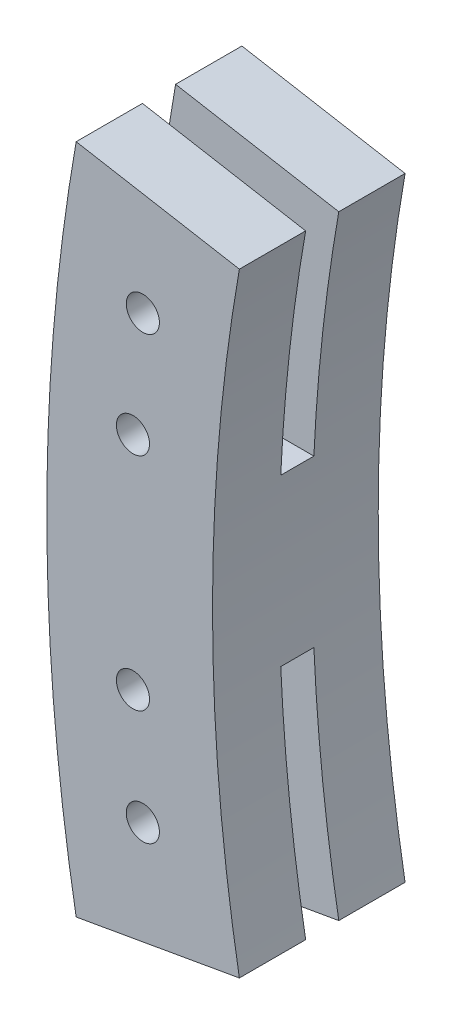
SolidWorks part; units mm, degrees
ref_plane "Front Plane" through (0, 0, 0) normal (0, 0, 1) x (1, 0, 0)
ref_plane "Top Plane" through (0, 0, 0) normal (0, 1, 0) x (1, 0, 0)
ref_plane "Right Plane" through (0, 0, 0) normal (1, 0, 0) x (0, 0, -1)
sketch "Sketch1" plane through (0, 0, 0) normal (0, 0, 1) x (1, 0, 0)
  line L0 (160, 0) -> (-167.5, 0) construction
  line L1 (0, 160) -> (0, -160) construction
  line L2 (0, 0) -> (-157.5692, 27.7837) construction
  line L3 (0, 0) -> (-157.5692, -27.7837) construction
  line L4 (-157.5692, 27.7837) -> (-172.3414, 30.3884)
  line L5 (-157.5692, -27.7837) -> (-172.3414, -30.3884)
  arc A0 (-157.5692, 27.7837) -> (-157.5692, -27.7837) centre (0, 0) ccw
  arc A1 (-172.3414, 30.3884) -> (-172.3414, -30.3884) centre (0, 0) ccw
  circle A2 centre (0, 0) radius 167.5 construction
  dimension "D1" = 320
  dimension "D2" = 350
  dimension "D4" = 7.5
  dimension "D3" = 20
extrude "Boss-Extrude3" add sketch "Sketch1" along normal mid plane 15 contours L4 A1 A0 | A1 L5 A0 | A1 A0 region at (-166.7623, 0, 0)
extrude "Cut-Extrude4" cut sketch "Sketch1<6>" against normal mid plane 3
sketch "Sketch1<6>" plane through (0, 0, 0) normal (0, 0, 1) x (1, 0, 0) same geometry as "Sketch1"
sketch "Sketch6" plane through (0, 0, 0) normal (0, 0, 1) x (1, 0, 0)
  line L1 (-184.1488, 7.5) -> (-150.8512, 7.5)
  line L2 (-184.1488, 7.5) -> (-184.1488, -7.5)
  line L3 (-184.1488, -7.5) -> (-150.8512, -7.5)
  line L4 (-150.8512, 7.5) -> (-150.8512, -7.5)
  line L5 (-184.1488, 7.5) -> (-150.8512, -7.5) construction
  line L6 (-184.1488, -7.5) -> (-150.8512, 7.5) construction
  arc A0 (-172.3414, 30.3884) -> (-172.3414, -30.3884) centre (0, 0) ccw construction
  arc A1 (-157.5692, 27.7837) -> (-157.5692, -27.7837) centre (0, 0) ccw construction
  arc A2 (-172.3414, 30.3884) -> (-172.3414, -30.3884) centre (0, 0) ccw
  arc A3 (-157.5692, 27.7837) -> (-157.5692, -27.7837) centre (0, 0) ccw
  point P0 (-167.5, 0)
  dimension "D1" = 15
extrude "Boss-Extrude5" add sketch "Sketch6" along normal mid plane 3 contours A3 L1 A2 L3 region at (-167.4439, 0, 0)
ref_plane "Plane1" through (-167.5, 0, 0) normal (1, 0, 0) x (0, 0, -1)
sketch "Sketch4" plane through (-167.5, 0, 0) normal (1, 0, 0) x (0, 0, -1)
  circle A0 centre (0, 0) radius 3
  dimension "D1" = 6
extrude "bearing hole" [suppressed] cut sketch "Sketch4" against normal mid plane 2.5
sketch "Sketch7" plane through (-167.5, 0, 0) normal (1, 0, 0) x (0, 0, -1)
  circle A0 centre (0, 0) radius 1.5
  dimension "D1" = 3
extrude "shaft hole" cut sketch "Sketch7" against normal up to surface (7.5 mm away) up to face at (-173.7427, 0, 0)
sketch "Sketch8" plane through (0, 0, 0) normal (0, 0, 1) x (1, 0, 0)
  line L0 (-160, 0) -> (-175, 0)
  line L2 (-157.5692, 27.7837) -> (-172.3414, 30.3884)
  line L3 (-172.3414, -30.3884) -> (-157.5692, -27.7837)
  line L4 (-157.5692, 27.7837) -> (-172.3414, 30.3884) construction
  line L5 (-172.3414, -30.3884) -> (-157.5692, -27.7837) construction
  arc A0 (-164.9553, 29.0861) -> (-164.9553, -29.0861) centre (0, 0) ccw construction
  arc A1 (-172.3414, 30.3884) -> (-172.3414, -30.3884) centre (0, 0) ccw construction
  circle A2 centre (-166.3065, 19.9599) radius 1.5
  circle A3 centre (-167.2012, 10) radius 1.5
  arc A4 (-157.5692, 27.7837) -> (-157.5692, -27.7837) centre (0, 0) ccw
  arc A5 (-172.3414, 30.3884) -> (-172.3414, -30.3884) centre (0, 0) ccw
  arc A6 (-157.5692, 27.7837) -> (-157.5692, -27.7837) centre (0, 0) ccw construction
  arc A7 (-172.3414, 30.3884) -> (-172.3414, -30.3884) centre (0, 0) ccw construction
  circle A8 centre (-167.2012, -10) radius 1.5
  circle A9 centre (-166.3065, -19.9599) radius 1.5
  dimension "D1" = 7.5
  dimension "D3" = 3
  dimension "D4" = 10
  dimension "D5" = 10
  dimension "D2" = 0
extrude "Cut-Extrude6" cut sketch "Sketch8" against normal through all both and the other way through all contours A2 | A3 | A8 | A9
